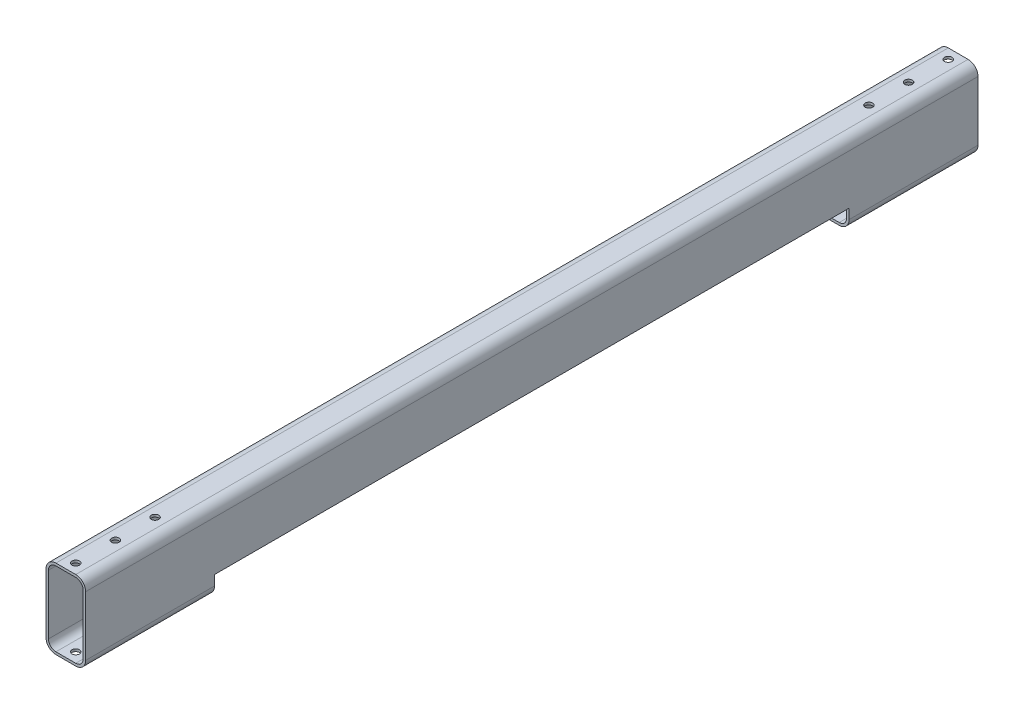
SolidWorks part; units mm, degrees
material "6061-T6 (SS)"
ref_plane "Front Plane" through (0, 0, 0) normal (0, 0, 1) x (1, 0, 0)
ref_plane "Top Plane" through (0, 0, 0) normal (0, 1, 0) x (1, 0, 0)
ref_plane "Right Plane" through (0, 0, 0) normal (1, 0, 0) x (0, 0, -1)
sketch "Sketch1" plane through (0, 0, 0) normal (0, 0, 1) x (1, 0, 0)
  line L1 (-6.35, -25.4) -> (6.35, -25.4)
  line L2 (-12.7, -19.05) -> (-12.7, 19.05)
  line L3 (-6.35, 25.4) -> (6.35, 25.4)
  line L4 (12.7, -19.05) -> (12.7, 19.05)
  line L5 (-12.7, -25.4) -> (12.7, 25.4) construction
  line L6 (-12.7, 25.4) -> (12.7, -25.4) construction
  arc A0 (-12.7, -19.05) -> (-6.35, -25.4) centre (-6.35, -19.05) ccw
  arc A1 (6.35, -25.4) -> (12.7, -19.05) centre (6.35, -19.05) ccw
  arc A2 (6.35, 25.4) -> (12.7, 19.05) centre (6.35, 19.05) cw
  arc A3 (-12.7, 19.05) -> (-6.35, 25.4) centre (-6.35, 19.05) cw
  point P0 (0, 0)
  dimension "D3" = 6.35
  dimension "D1" = 50.8
  dimension "D2" = 25.4
extrude "Extrude-Thin1" add sketch "Sketch1" along normal blind 571.5 thin thin type one direction reverse wall 1.5875
hole_wizard "3/16 (0.1875) Diameter Hole1" positions "3DSketch1" profile "Sketch3" hole size "3/16" standard "ANSI Inch" end condition through all
sketch3d "3DSketch1"
  line L1 (6.35, 25.4, 0) -> (-6.35, 25.4, 0) construction
  line L6 (0, 25.4, 571.5) -> (0, 25.4, 0) construction
  line L7 (6.35, 25.4, 571.5) -> (-6.35, 25.4, 571.5) construction
  point P57 (0, 25.4, 6.35)
  point P59 (0, 25.4, 31.75)
  point P61 (0, 25.4, 57.15)
  point P63 (0, 25.4, 539.75)
  point P65 (0, 25.4, 514.35)
  point P67 (0, 25.4, 565.15)
  dimension "D1" = 25.4
  dimension "D2" = 25.4
  dimension "D3" = 6.35
  dimension "D4" = 25.4
  dimension "D5" = 25.4
  dimension "D6" = 6.35
sketch "Sketch3" plane through (0, 25.4, 565.15) normal (1, 0, 0) x (0, 0, 1)
  line L0 (0, 0) -> (0, 50.8)
  line L1 (0, 50.8) -> (2.3812, 50.8)
  line L2 (2.3812, 50.8) -> (2.3812, 0)
  line L5 (2.3812, 0) -> (0, 0)
  line L11 (0, -6.35) -> (0, 107.95) construction
  dimension "Thru Hole Dia." = 4.7625
  dimension "Thru Hole Depth" = 50.8
sketch "Sketch5" plane through (12.7, 0, 0) normal (1, 0, 0) x (0, 0, -1)
  line L0 (-488.95, -12.7) -> (-488.95, -25.4)
  line L2 (-488.95, -25.4) -> (-82.55, -25.4)
  line L3 (-82.55, -25.4) -> (-82.55, -12.7)
  line L4 (-82.55, -12.7) -> (-488.95, -12.7)
  line L12 (-571.5, -25.4) -> (0, -25.4) construction
  point P11 (-285.75, -25.4)
  point P12 (-285.75, -25.4)
  dimension "D1" = 12.7
  dimension "D2" = 406.4
extrude "Cut-Extrude1" cut sketch "Sketch5" against normal through all
hole_wizard "3/16 (0.195) Diameter Hole1" positions "Sketch6" profile "Sketch7" hole size "3/16" standard "ANSI Inch"
sketch "Sketch6" plane through (0, -25.4, 0) normal (0, -1, 0) x (-1, 0, 0)
  point P0 (2.54, -495.3)
  point P3 (-5.08, -502.92)
  point P6 (-5.08, -68.58)
  point P9 (2.54, -76.2)
sketch "Sketch7" plane through (-2.54, -25.4, 495.3) normal (1, 0, 0) x (0, 0, -1)
  line L0 (0, 0) -> (0, 26.888)
  line L1 (0, 26.888) -> (2.4765, 25.4)
  line L2 (2.4765, 25.4) -> (2.4765, 0)
  line L5 (2.4765, 0) -> (0, 0)
  line L10 (0, 26.888) -> (-2.4765, 25.4) construction
  line L11 (0, -6.35) -> (0, 107.95) construction
  dimension "Hole Dia." = 4.953
  dimension "Hole Depth" = 25.4
  dimension "Drill Angle" = 118
